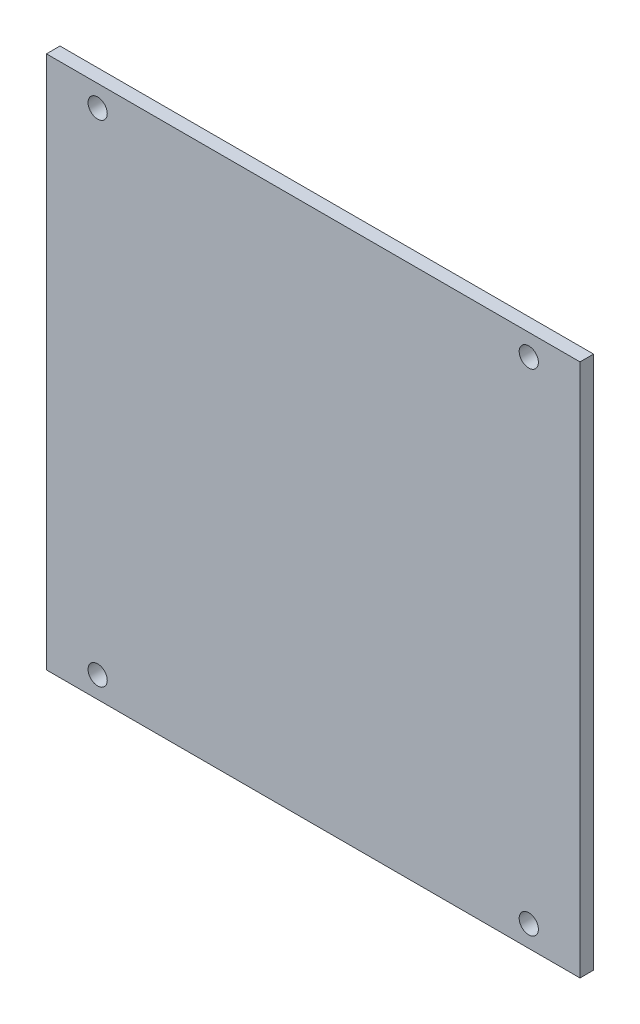
SolidWorks part; units mm, degrees
ref_plane "Plan de face" through (0, 0, 0) normal (0, 0, 1) x (1, 0, 0)
ref_plane "Plan de dessus" through (0, 0, 0) normal (0, 1, 0) x (1, 0, 0)
ref_plane "Plan de droite" through (0, 0, 0) normal (1, 0, 0) x (0, 0, -1)
sketch "Sketch1" plane through (0, 0, 0) normal (0, 0, 1) x (1, 0, 0)
  line L1 (62.5, -62.5) -> (-62.5, -62.5)
  line L2 (62.5, -62.5) -> (62.5, 62.5)
  line L3 (62.5, 62.5) -> (-62.5, 62.5)
  line L4 (-62.5, -62.5) -> (-62.5, 62.5)
  line L5 (62.5, -62.5) -> (-62.5, 62.5) construction
  line L6 (62.5, 62.5) -> (-62.5, -62.5) construction
  point P0 (0, 0)
  dimension "D1" = 125
  dimension "D2" = 125
extrude "Boss-Extrude1" add sketch "Sketch1" along normal blind 3.175
sketch "Sketch2" plane through (0, 0, 3.175) normal (0, 0, 1) x (1, 0, 0)
  line L0 (0, -62.5) -> (0, 62.5) construction
  line L1 (-62.5, -62.5) -> (62.5, -62.5) construction
  line L2 (62.5, 62.5) -> (-62.5, 62.5) construction
  line L3 (-62.5, 62.5) -> (-62.5, -62.5) construction
  circle A0 centre (-50.5, 57.5) radius 2.25
  circle A1 centre (-50.5, -57.5) radius 2.25
  circle A4 centre (50.5, -57.5) radius 2.25
  circle A5 centre (50.5, 57.5) radius 2.25
  point P14 (0, 0)
  point P15 (-58.6715, -27.0158)
  dimension "D5" = 4.5
  dimension "D6" = 4.5
  dimension "D1" = 5
  dimension "D2" = 12
  dimension "D3" = 12
  dimension "D4" = 5
extrude "Cut-Extrude2" cut sketch "Sketch2" against normal blind 3.175
